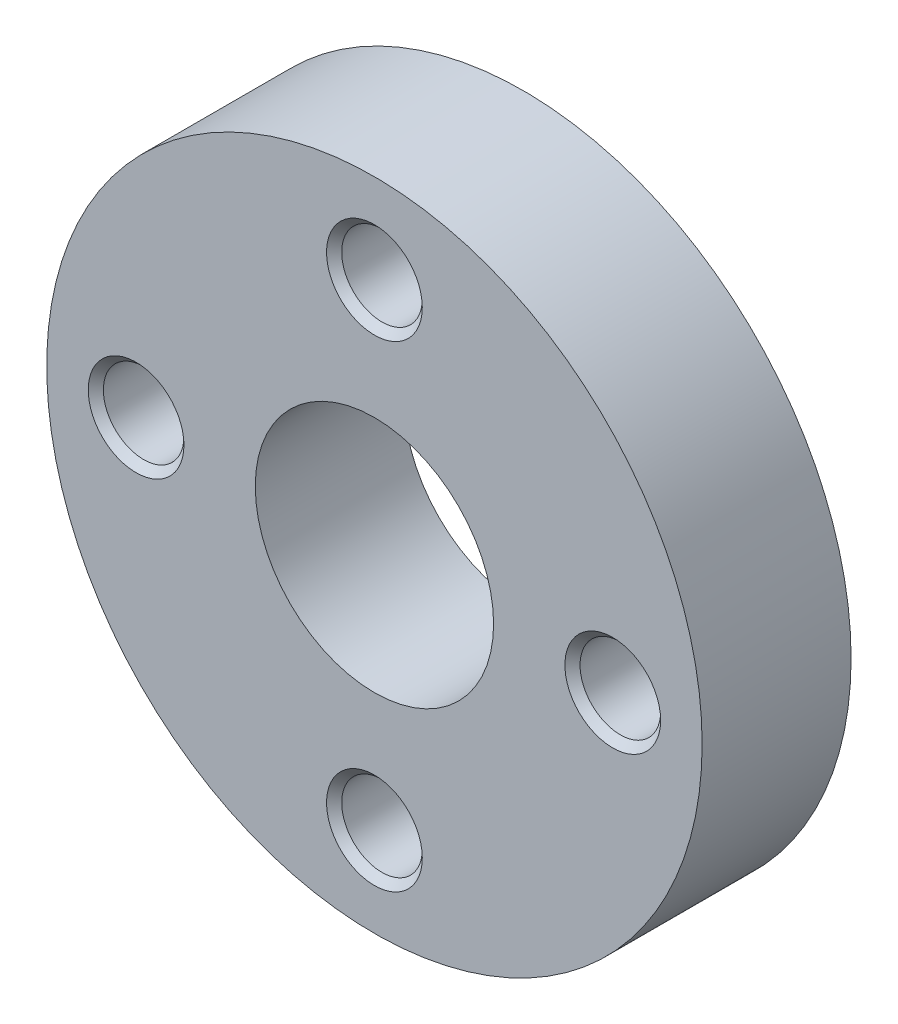
SolidWorks part; units mm, degrees
material "6061-T6 (SS)"
ref_plane "Front Plane" through (0, 0, 0) normal (0, 0, 1) x (1, 0, 0)
ref_plane "Top Plane" through (0, 0, 0) normal (0, 1, 0) x (1, 0, 0)
ref_plane "Right Plane" through (0, 0, 0) normal (1, 0, 0) x (0, 0, -1)
sketch "Sketch1" plane through (0, 0, 0) normal (0, 0, 1) x (1, 0, 0)
  circle A0 centre (0, 0) radius 11
  dimension "D1" = 22
extrude "Extrude1" add sketch "Sketch1" against normal blind 5
sketch "Sketch2" plane through (0, 0, 0) normal (0, 0, 1) x (1, 0, 0)
  circle A0 centre (0, 0) radius 4
  dimension "D1" = 8
hole_wizard "#6-32 Tapped Hole3" positions "3DSketch4" profile "Sketch7" tap size "#6-32" standard "Ansi Inch" end condition through all
sketch3d "3DSketch4"
  line L0 (0, 0, 0) -> (13.2813, 0, 0) construction
  line L1 (13.2813, 0, 0) -> (-13.4508, 0, 0) construction
  line L3 (0, 0, 0) -> (0, -11.5868, 0) construction
  line L4 (0, -11.5868, 0) -> (0, 11.7986, 0) construction
  point P0 (0, 8, 0)
  point P2 (-8, 0, 0)
  point P4 (8, 0, 0)
  point P6 (0, -8, 0)
  dimension "D1" = 8
  dimension "D2" = 8
  dimension "D3" = 8
  dimension "D4" = 8
sketch "Sketch7" plane through (0, 8, 0) normal (1, 0, 0) x (0, -1, 0)
  line L0 (0, 0) -> (0, 5)
  line L1 (0, 5) -> (1.3525, 5)
  line L2 (1.3525, 5) -> (1.3525, 0)
  line L5 (1.3525, 0) -> (0, 0)
  line L11 (0, -6.35) -> (0, 107.95) construction
  dimension "Thru Tap Drill Dia." = 2.7051
  dimension "Thru Tap Drill Depth" = 5
cosmetic thread "Hole Thread4" parameters "D2"=3.5052
cosmetic thread "Hole Thread5" parameters "D2"=3.5052
cosmetic thread "Hole Thread6" parameters "D2"=3.5052
cosmetic thread "Hole Thread7" parameters "D2"=3.5052
chamfer "Chamfer1" distance 0.254 angle 45 8 edges at (1.3525, 8, 0) (1.3525, -8, -5) (-6.6475, 0, -5) (1.3525, 8, -5) (9.3525, 0, -5) (9.3525, 0, 0) (1.3525, -8, 0) (-6.6475, 0, 0)
extrude "Extrude2" cut sketch "Sketch2" against normal through all
